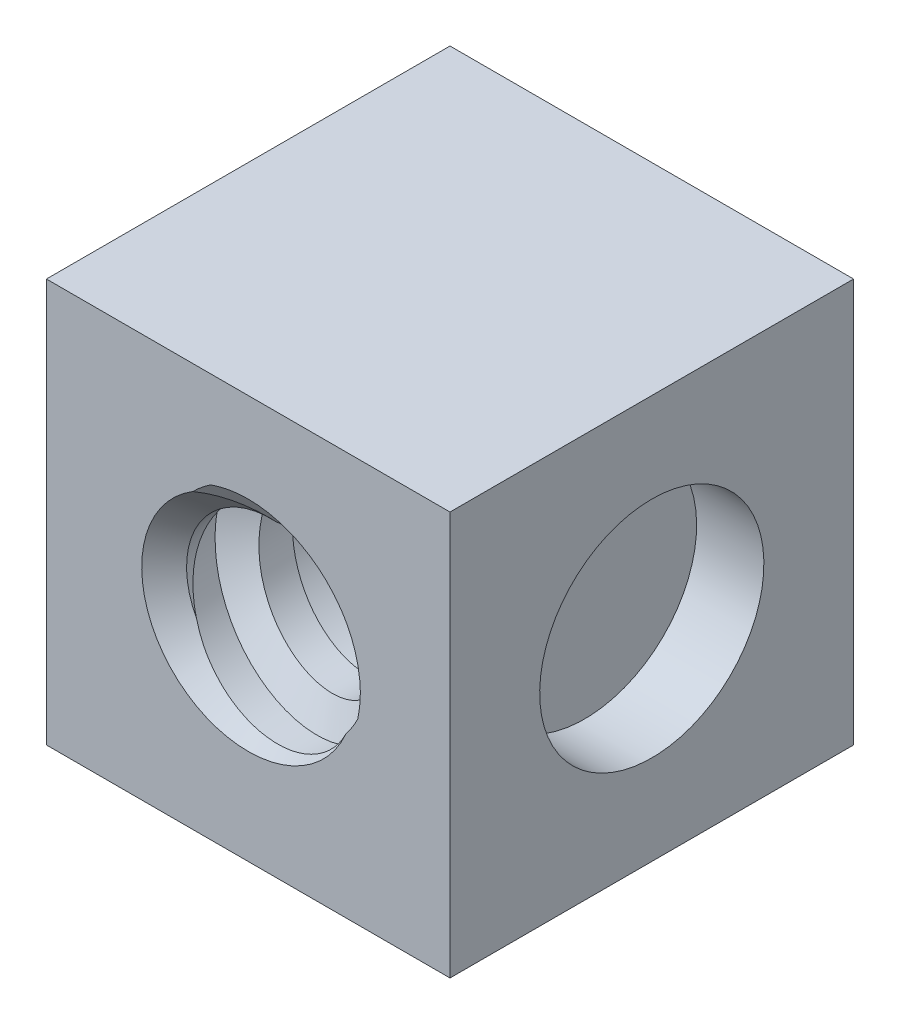
SolidWorks part; units mm, degrees
ref_plane "Front Plane" through (0, 0, 0) normal (0, 0, 1) x (1, 0, 0)
ref_plane "Top Plane" through (0, 0, 0) normal (0, 1, 0) x (1, 0, 0)
ref_plane "Right Plane" through (0, 0, 0) normal (1, 0, 0) x (0, 0, -1)
sketch "Sketch1" plane through (0, 0, 0) normal (0, 0, 1) x (1, 0, 0)
  line L1 (-9, 9) -> (9, 9)
  line L2 (-9, 9) -> (-9, -9)
  line L3 (-9, -9) -> (9, -9)
  line L4 (9, 9) -> (9, -9)
  line L5 (-9, 9) -> (9, -9) construction
  line L6 (-9, -9) -> (9, 9) construction
  circle A0 centre (0, 0) radius 3.75
  point P0 (0, 0)
  dimension "D3" = 7.5
  dimension "D1" = 18
  dimension "D2" = 18
extrude "Boss-Extrude1" add sketch "Sketch1" along normal blind 18
sketch "Sketch2" plane through (9, 0, 0) normal (1, 0, 0) x (0, 0, -1)
  line L0 (-18, -9) -> (0, -9) construction
  circle A0 centre (-9, 0) radius 5
  point P5 (-9, -9)
  dimension "D1" = 10
extrude "Cut-Extrude1" cut sketch "Sketch2" against normal blind 3
mirror "Mirror1" about plane through (0, 0, 0) normal (1, 0, 0) of "Cut-Extrude1"
sketch "Sketch3" plane through (0, 0, 0) normal (1, 0, 0) x (0, 0, -1)
  line L0 (2.2217, -5) -> (2.9434, -3.75)
  line L1 (2.9434, -3.75) -> (0, -3.75)
  line L2 (0, -3.75) -> (0.7217, -5)
  line L3 (0.7217, -5) -> (2.2217, -5)
  line L4 (1.4717, -3.75) -> (1.4717, -7.4531) construction
  line L5 (0, -3.75) -> (0, 3.75) construction
  point P6 (0.8273, -3.0302)
  point P7 (0, 0)
  point P10 (0, 0)
  point P11 (0, 0)
  point P12 (0, 0)
  dimension "D1" = 60
  dimension "D2" = 1.25
  dimension "D3" = 1.5
  dimension "D4" = 3.75
sketch "Sketch4" plane through (0, 0, 0) normal (0, 0, -1) x (-1, 0, 0)
  circle A0 centre (0, 0) radius 3.75 construction
  circle A1 centre (0, 0) radius 3.75
curve "Helix/Spiral1" pitch 4.44 height 22 radius 3.75 centre (0, 0, 0) axis (0, 0, 1) start towards (-1, 0, 0)
sweep "Cut-Sweep2" cut profiles "Sketch3" path "Helix/Spiral1" align with end faces yes
chamfer "Chamfer1" distance 1 angle 45 1 edges
chamfer "Chamfer2" distance 1 angle 45 1 edges
